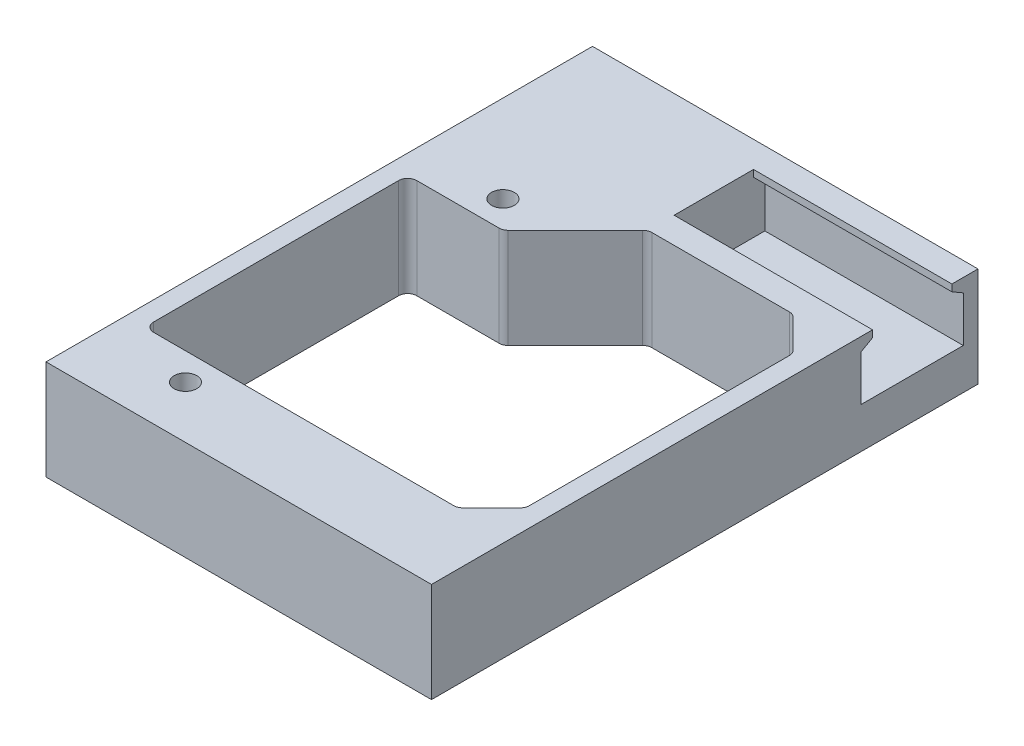
SolidWorks part; units mm, degrees
ref_plane "Front Plane" through (0, 0, 0) normal (0, 0, 1) x (1, 0, 0)
ref_plane "Top Plane" through (0, 0, 0) normal (0, 1, 0) x (1, 0, 0)
ref_plane "Right Plane" through (0, 0, 0) normal (1, 0, 0) x (0, 0, -1)
sketch "Sketch1" plane through (0, 0, 0) normal (0, 1, 0) x (1, 0, 0)
  line L0 (0, 0) -> (0, 59.6401) construction
  line L1 (-20, -19.2885) -> (-21.7, -19.2885)
  line L2 (20, 17.7115) -> (21.7, 17.7115)
  line L3 (20, 17.7115) -> (20, 69.9115)
  line L4 (20, 69.9115) -> (21.7, 69.9115)
  line L5 (21.7, 17.7115) -> (21.7, 69.9115)
  line L6 (20, 17.7115) -> (21.7, 17.7115)
  line L7 (20, 17.7115) -> (20, -19.2885)
  line L8 (20, -19.2885) -> (21.7, -19.2885)
  line L9 (21.7, 17.7115) -> (21.7, -19.2885)
  line L10 (-21.7, 17.7115) -> (-21.7, -19.2885)
  line L11 (-20, 17.7115) -> (-21.7, 17.7115)
  line L12 (-20, 17.7115) -> (-20, -19.2885)
  line L13 (-20, 69.9115) -> (-21.7, 69.9115)
  line L14 (-21.7, 17.7115) -> (-21.7, 69.9115)
  line L15 (-20, 17.7115) -> (-21.7, 17.7115)
  line L16 (-20, 17.7115) -> (-20, 69.9115)
  dimension "18" = 20
  dimension "D2" = 1.7
  dimension "D3" = 37
  dimension "D4" = 52.2
extrude "Boss-Extrude1" add sketch "Sketch1" against normal blind 8.8 from offset 1 contours L12 L11 L10 L1 | L11 L16 L13 L14 | L3 L2 L5 L4 offset against normal yes
sketch "Sketch4" plane through (0, -9.8, 0) normal (0, -1, 0) x (1, 0, 0)
  line L0 (-21.7, -69.9115) -> (-21.7, 19.2885) construction
  line L1 (12, -69.9115) -> (-21.7, -69.9115)
  line L2 (12, -69.9115) -> (12, -58.3115)
  line L3 (12, -58.3115) -> (-21.7, -58.3115)
  line L4 (-21.7, -69.9115) -> (-21.7, -58.3115)
  line L10 (-20, -69.9115) -> (-20, 19.2885) construction
  line L13 (-20, -69.9115) -> (-21.7, -69.9115) construction
  dimension "D1" = 11.6
  dimension "D2" = 32
extrude "Boss-Extrude3" add sketch "Sketch4" against normal up to surface (8.8 mm away)
sketch "Sketch3" plane through (0, -9.8, 0) normal (0, -1, 0) x (1, 0, 0)
  line L0 (-21.7, -69.9115) -> (-21.7, 19.2885) construction
  line L1 (-21.7, -58.9115) -> (-7.7, -58.9115)
  line L2 (-21.7, -58.9115) -> (-21.7, -51.9115)
  line L3 (-21.7, -51.9115) -> (-7.7, -51.9115)
  line L4 (-7.7, -58.9115) -> (-7.7, -51.9115)
  line L6 (0, 0) -> (0, -31.4212) construction
  line L13 (12, -69.9115) -> (-21.7, -69.9115) construction
  line L14 (-21.7, -40.3115) -> (-3.8096, -40.3115) construction
  line L15 (-21.7, -28.7115) -> (-7.7, -28.7115)
  line L16 (-7.7, -21.7115) -> (-7.7, -28.7115)
  line L17 (-21.7, -21.7115) -> (-7.7, -21.7115)
  line L18 (-21.7, -21.7115) -> (-21.7, -28.7115)
  line L19 (-20, -58.3115) -> (-20, 19.2885) construction
  circle A0 centre (-14, -54.3115) radius 1
  circle A2 centre (-14, -26.3115) radius 1
  dimension "D4" = 2.4
  dimension "D5" = 2
  dimension "D1" = 14
  dimension "D2" = 15.6
  dimension "D3" = 7
  dimension "D6" = 6
  dimension "D7" = 14
extrude "Servo Holder" add sketch "Sketch3" along normal blind 1 and the other way offset from surface (8.8 mm away) 1 other way up to plane "Top Plane"
sketch "Sketch37" plane through (0, -1, 0) normal (0, 1, 0) x (1, 0, 0)
  line L0 (-7.7, 21.7115) -> (-20, 21.7115) construction
  line L1 (12.3, 21.7115) -> (-7.7, 21.7115)
  line L2 (12.3, 21.7115) -> (12.3, 28.7115)
  line L3 (12.3, 28.7115) -> (-7.7, 28.7115)
  line L4 (-7.7, 21.7115) -> (-7.7, 28.7115)
  line L5 (-21.7, 69.9115) -> (-21.7, -19.2885) construction
  dimension "D1" = 34
extrude "Boss-Extrude19" add sketch "Sketch37" against normal up to surface (9.8 mm away) up to face at (-14.7, -10.8, -25.2115)
sketch "Sketch29" plane through (0, 0, -69.9115) normal (0, 0, -1) x (-1, 0, 0)
  line L1 (21.7, -9.8) -> (-12.7099, -9.8)
  line L2 (21.7, -9.8) -> (21.7, -16.1774)
  line L3 (21.7, -16.1774) -> (-12.7099, -16.1774)
  line L4 (-12.7099, -9.8) -> (-12.7099, -16.1774)
extrude "Cut-Extrude10" cut sketch "Sketch29" against normal through all both and the other way through all
sketch "Sketch30" plane through (0, 0, 0) normal (0, 0, 1) x (1, 0, 0)
  line L0 (-4.7, -1) -> (-4.7, -39) construction
  line L1 (12.3, -1) -> (-21.7, -1)
  line L2 (12.3, -1) -> (12.3, -39)
  line L3 (12.3, -39) -> (-21.7, -39)
  line L4 (-21.7, -1) -> (-21.7, -39)
  line L7 (-21.7, -1) -> (12.3, -1) construction
  line L9 (12.3, -1) -> (-20, -1) construction
  line L11 (-21.7, -9.8) -> (-21.7, -1) construction
  circle A0 centre (5.3, -34) radius 1.6
  circle A1 centre (5.3, -19) radius 1.6
  circle A2 centre (-14.7, -34) radius 1.6
  circle A3 centre (-14.7, -19) radius 1.6
  dimension "D2" = 10
  dimension "D4" = 15
  dimension "D1" = 17
  dimension "D3" = 38
  dimension "D5" = 18
  dimension "D6" = 10
extrude "Boss-Extrude13" add sketch "Sketch30" along normal blind 6.5 from offset 2 separate body
sketch "Sketch41" plane through (-20, 0, 0) normal (1, 0, 0) x (0, 0, -1)
  line L0 (21.7115, -1) -> (-19.2885, -1) construction
  line L1 (-2, -1) -> (-19.2885, -1)
  line L2 (-2, -1) -> (-2, -9.8)
  line L3 (-2, -9.8) -> (-19.2885, -9.8)
  line L4 (-19.2885, -1) -> (-19.2885, -9.8)
  line L5 (-2, -1) -> (-2, -39) construction
extrude "Cut-Extrude14" cut sketch "Sketch41" against normal blind 15
sketch "Sketch32" plane through (0, -39, 0) normal (0, -1, 0) x (1, 0, 0)
  line L1 (22.55, 8.5) -> (12.9564, 0.4867) construction
  line L2 (22.55, 8.5) -> (12.3, 8.5) construction
  line L4 (-21.7, 8.5) -> (12.3, 8.5) construction
  circle A0 centre (22.55, 8.5) radius 5
  circle A1 centre (22.55, 8.5) radius 12.5
  circle A2 centre (15.2588, 2.4099) radius 1.45
  circle A3 centre (16.4599, 15.7912) radius 1.45
  circle A4 centre (29.8412, 14.5901) radius 1.45
  circle A5 centre (28.6401, 1.2088) radius 1.45
  point P18 (22.55, 8.5)
  line M1 (-21.7, 2) -> (12.3, 2)
  line M2 (12.3, 2) -> (12.3, 8.5)
  line M3 (12.3, 8.5) -> (-21.7, 8.5)
  dimension "D1" = 9.5
  dimension "D2" = 25
  dimension "D4" = 10
  dimension "D5" = 10.25
  dimension "D3" = 4
extrude "Boss-Extrude14" add sketch "Sketch32" along normal blind 8.8 from surface at -38 contours A1 A5 A4 A3 A2 A0 M1 M3 M2 starting at face at (-3.85, -1, 5.25)
sketch "Sketch34" plane through (-21.7, 0, 0) normal (-1, 0, 0) x (0, 0, 1)
  line L1 (-21.7115, -1) -> (-21.7115, -9.8)
  line L5 (-69.9115, -1) -> (2, -1) construction
  line L7 (-21.7115, -9.8) -> (2, -39)
  line L8 (-21.7115, -9.8) -> (-21.7115, -1) construction
  line L9 (2, -39) -> (8.5, -39)
  line L10 (8.5, -39) -> (8.5, -1)
  line L11 (8.5, -1) -> (-21.7115, -1)
extrude "Boss-Extrude16" add sketch "Sketch34" against normal blind 3
sketch "Sketch35" plane through (12.3, 0, 0) normal (1, 0, 0) x (0, 0, -1)
  line L0 (-2, -1) -> (21.7115, -1)
  line L1 (21.7115, -1) -> (21.7115, -9.8)
  line L3 (-8.5, -9.8) -> (-8.5, -1)
  line L4 (-8.5, -1) -> (-2, -1)
  line L5 (21.7115, -9.8) -> (21.7115, -1) construction
  line L8 (-8.5, -39) -> (-8.5, -9.8) construction
  line L9 (21.7115, -1) -> (28.7115, -1) construction
  line L10 (21.7115, -9.8) -> (-2, -39)
  line L11 (-2, -39) -> (-8.5, -39)
  line L12 (-8.5, -39) -> (-8.5, -9.8)
extrude "Boss-Extrude17" add sketch "Sketch35" against normal blind 3
sketch "Sketch36" plane through (0, -9.8, 0) normal (0, -1, 0) x (1, 0, 0)
  line L0 (12.3, -10.5792) -> (16.6342, -2.5115)
  line L2 (16.6342, -2.5115) -> (12.3, 1.3455)
  line L3 (12.3, 1.3455) -> (12.3, -10.5792)
  line L4 (22.55, 8.5) -> (12.3, -10.5792) construction
  line L5 (12.3, 8.5) -> (12.3, 2) construction
  arc A1 (12.3, 1.3455) -> (10.05, 8.5) centre (22.55, 8.5) ccw construction
extrude "Boss-Extrude18" add sketch "Sketch36" against normal up to surface (8.8 mm away) up to face at (-4.7, -1, -9.8558)
fillet "Fillet9" [suppressed] radius 1
sketch "Sketch39" plane through (0, -1, 0) normal (0, 1, 0) x (1, 0, 0)
  line L0 (-21.7, 69.9115) -> (12, 69.9115) construction
  line L1 (12.3, 28.7115) -> (10.6, 28.7115)
  line L2 (12.3, 28.7115) -> (12.3, 69.9115)
  line L3 (12.3, 69.9115) -> (10.6, 69.9115)
  line L4 (10.6, 28.7115) -> (10.6, 69.9115)
  line L5 (-20, 28.7115) -> (12.3, 28.7115) construction
  line L6 (12.3, 10.5792) -> (12.3, 28.7115) construction
  point P7 (12.3, 49.3115)
  dimension "D1" = 1.7
extrude "Boss-Extrude20" add sketch "Sketch39" against normal up to surface (8.8 mm away) up to face at (-4.9667, -9.8, -42.0449)
sketch "Sketch40" plane through (12.3, 0, 0) normal (1, 0, 0) x (0, 0, -1)
  line L1 (60.6115, -1) -> (67.6115, -1)
  line L6 (60.6115, -2.2) -> (59.6115, -2.2)
  line L7 (59.6115, -2.2) -> (59.6115, -6.2)
  line L8 (59.6115, -6.2) -> (68.6115, -6.2)
  line L9 (64.1115, -6.2) -> (64.1115, -1)
  line L11 (68.6115, -2.2) -> (68.6115, -6.2)
  line L12 (67.6115, -2.2) -> (68.6115, -2.2)
  line L13 (67.6115, -1) -> (67.6115, -2.2)
  line L14 (69.9115, -9.8) -> (69.9115, -1) construction
  line L15 (60.6115, -2.2) -> (60.6115, -1)
  line L16 (10.5792, -1) -> (69.9115, -1) construction
  point P9 (59.6115, -4.2)
  dimension "D1" = 5.8
  dimension "D2" = 3.5
  dimension "D3" = 4.5
  dimension "D4" = 4
  dimension "D5" = 1.2
  dimension "D6" = 3.5
  dimension "D7" = 1
extrude "Cut-Extrude13" cut sketch "Sketch40" against normal blind 17.5
chamfer "Chamfer2" distance 0.6 angle 60 2 edges at (3.55, -2.2, -67.6115) (3.55, -2.2, -60.6115)
chamfer "Chamfer3" distance 3 angle 45 2 edges at (10.6, -5.4, -28.7115) (10.6, -5.4, -58.3115)
fillet "Fillet10" radius 6 2 edges at (16.6342, -5.4, -2.5115) (12.3, -5.4, -10.5792)
sketch "Sketch42" plane through (0, 0, 8.5) normal (0, 0, 1) x (1, 0, 0)
  line L0 (-4.7, -39) -> (-4.7, -1) construction
  line L3 (-21.7, -39) -> (12.3, -39) construction
  line L4 (10.05, -1) -> (-21.7, -1) construction
  line L5 (-1.1, -1) -> (-1.1, -10.6)
  line L6 (-8.3, -1) -> (-8.3, -10.6)
  line L7 (-1.1, -1) -> (-8.3, -1)
  arc A0 (-1.1, -10.6) -> (-8.3, -10.6) centre (-4.7, -10.6) cw
  point P11 (-4.7, -14.2)
  dimension "D1" = 3.6
  dimension "D2" = 13.2
extrude "Cut-Extrude15" cut sketch "Sketch42" against normal blind 10
chamfer "Chamfer4" distance 2.5 angle 45 1 edges at (-7.7, -5.4, -58.3115)
sketch "Sketch43" plane through (0, -1, 0) normal (0, 1, 0) x (1, 0, 0)
  line L0 (-5.2, 58.3115) -> (-11.6, 51.9115)
  line L1 (-7.7, 51.9115) -> (-20, 51.9115) construction
  line L2 (-11.6, 51.9115) -> (-5.2, 51.9115)
  line L3 (-5.2, 51.9115) -> (-5.2, 58.3115)
extrude "Cut-Extrude16" cut sketch "Sketch43" against normal blind 10
fillet "Fillet11" radius 0.8 8 edges at (-20, -5.4, -51.9115) (-20, -5.4, -28.7115) (7.6, -5.4, -28.7115) (10.6, -5.4, -31.7115) (10.6, -5.4, -55.3115) (7.6, -5.4, -58.3115) (-11.6, -5.4, -51.9115) (-5.2, -5.4, -58.3115)
sketch "Sketch44" plane through (0, -1, 0) normal (0, 1, 0) x (1, 0, 0)
  line L1 (37.4929, 21.7115) -> (-21.7, 21.7115)
  line L2 (37.4929, 21.7115) -> (37.4929, -23.7056)
  line L3 (37.4929, -23.7056) -> (-21.7, -23.7056)
  line L4 (-21.7, 21.7115) -> (-21.7, -23.7056)
  point P6 (0, 0)
extrude "Cut-Extrude17" cut sketch "Sketch44" against normal through all
